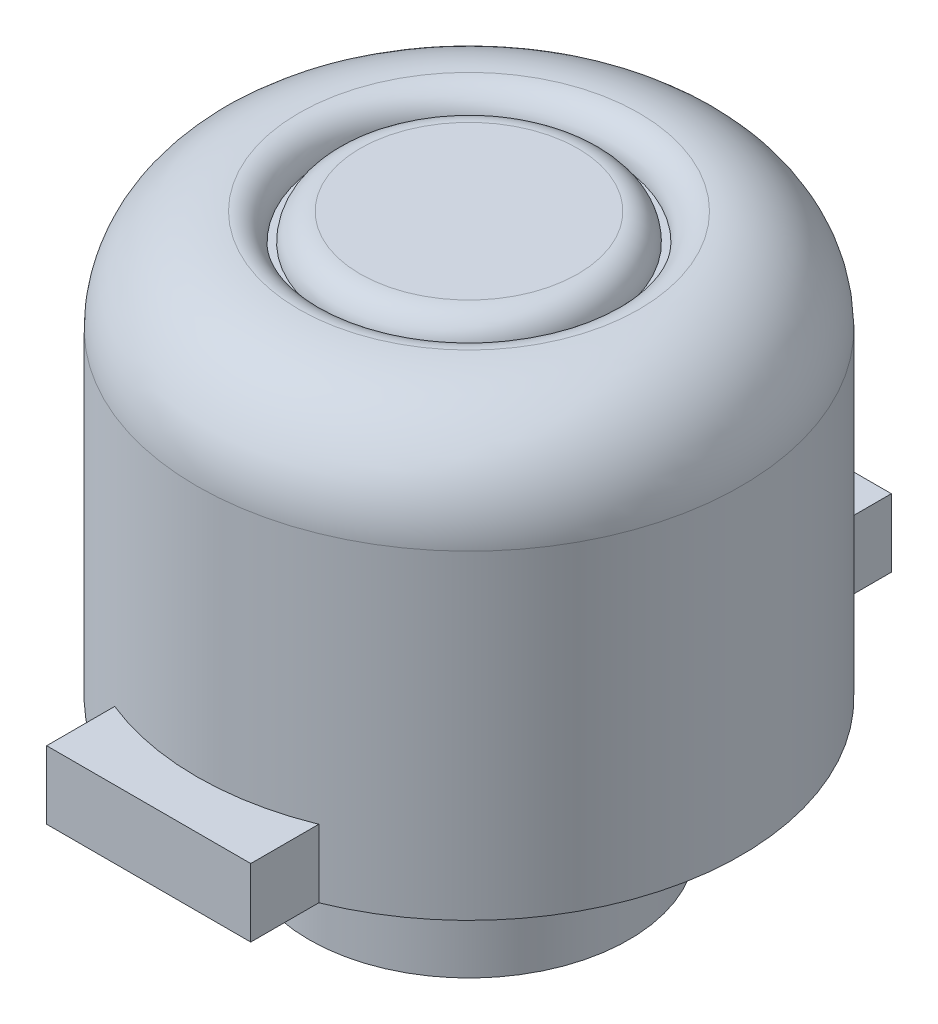
SolidWorks part; units mm, degrees
ref_plane "Front Plane" through (0, 0, 0) normal (0, 0, 1) x (1, 0, 0)
ref_plane "Top Plane" through (0, 0, 0) normal (0, 1, 0) x (1, 0, 0)
ref_plane "Right Plane" through (0, 0, 0) normal (1, 0, 0) x (0, 0, -1)
ref_axis "Axis1" through (0, 0, 0) along (0, 1, 0)
sketch "Sketch1" plane through (0, 0, 0) normal (0, 0, 1) x (1, 0, 0)
  line L1 (0, 0) -> (0, 69.0457) construction
  line L5 (4, 0) -> (2.35, 0)
  line L6 (2.35, 0) -> (2.35, 5.4)
  line L7 (2.35, 5.4) -> (0, 5.4)
  line L13 (4, 6.2) -> (4, 0)
  line L14 (4, 6.2) -> (0, 6.2)
  line L15 (0, 6.2) -> (0, 5.4)
  dimension "D1" = 0.8
  dimension "D2" = 1.65
  dimension "D3" = 4
  dimension "D4" = 5.4
revolve "Revolve1" add sketch "Sketch1" angle 360 about axis through (0, 0, 0) along (0, 1, 0)
sketch "Sketch3" plane through (0, 0, 0) normal (0, 1, 0) x (1, 0, 0)
  line L0 (0, 0) -> (0, -4.7081) construction
  line L2 (-1.5, -3.7081) -> (1.5, -3.7081)
  line L3 (-1.5, -3.7081) -> (-1.5, -4.7081)
  line L4 (-1.5, -4.7081) -> (1.5, -4.7081)
  line L5 (1.5, -3.7081) -> (1.5, -4.7081)
  circle A0 centre (0, 0) radius 4 construction
  dimension "D1" = 1
  dimension "D2" = 3
extrude "Boss-Extrude2" add sketch "Sketch3" along normal blind 1
mirror "Mirror2" about plane through (0, 0, 0) normal (0, 0, 1) of "Boss-Extrude2"
fillet "Fillet1" radius 1.5 1 edges at (0, 6.2, -4)
sketch "Sketch5" plane through (0, 6.2, 0) normal (0, 1, 0) x (1, 0, 0)
  circle A0 centre (0, 0) radius 2.1
  circle A1 centre (0, 0) radius 2
  dimension "D1" = 0.1
  dimension "D2" = 4
extrude "Cut-Extrude1" cut sketch "Sketch5" against normal blind 0.4
fillet "Fillet2" radius 0.4 2 edges at (0, 6.2, 2.1) (0, 6.2, 2)
sketch "Sketch6" plane through (0, 0, 0) normal (0, -1, 0) x (1, 0, 0)
  circle A0 centre (0, 0) radius 2.35
extrude "Boss-Extrude3" add sketch "Sketch6" along normal offset from surface 2.9 and the other way blind 4.4 up to face at (0, 1, 4.2811)
equation "\"D1@Boss-Extrude3\"=4.00-0.17-0.93"
